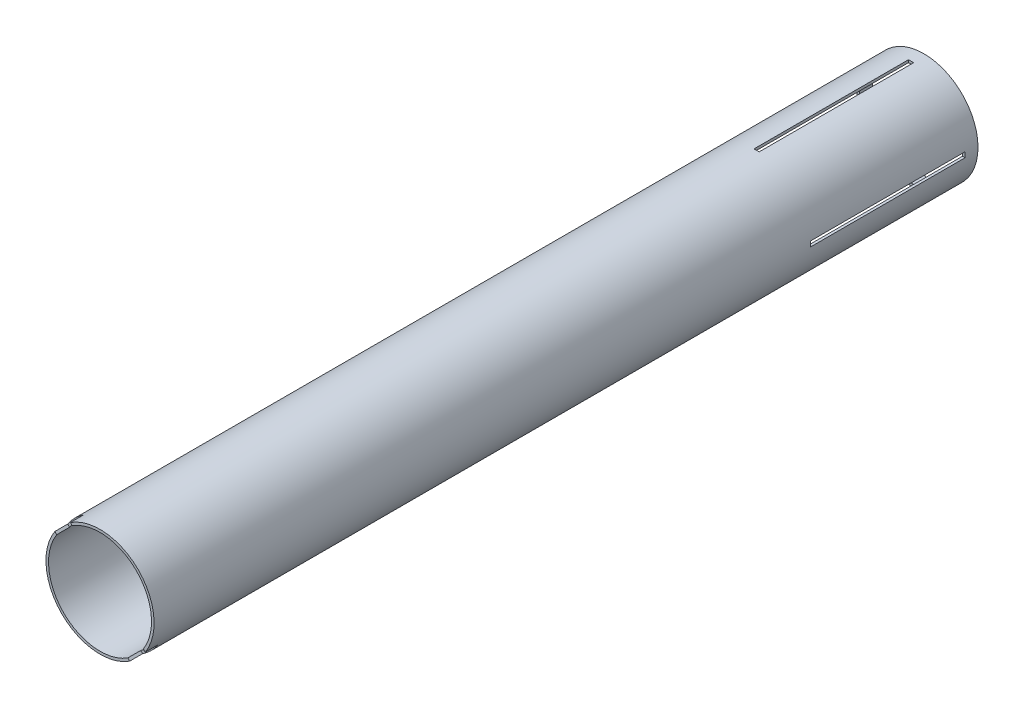
SolidWorks part; units mm, degrees
material "Corrugated Paper"
ref_plane "Front Plane" through (0, 0, 0) normal (0, 0, 1) x (1, 0, 0)
ref_plane "Top Plane" through (0, 0, 0) normal (0, 1, 0) x (1, 0, 0)
ref_plane "Right Plane" through (0, 0, 0) normal (1, 0, 0) x (0, 0, -1)
sketch "Sketch1" plane through (0, 0, 0) normal (0, 0, 1) x (1, 0, 0)
  circle A0 centre (0, 0) radius 50.8
  circle A1 centre (0, 0) radius 53.34
  dimension "D1" = 101.6
  dimension "D2" = 106.68
extrude "Boss-Extrude1" add sketch "Sketch1" along normal blind 812.8
sketch "Sketch2" plane through (0, 0, 0) normal (1, 0, 0) x (0, 0, -1)
  line L0 (0, -53.34) -> (0, 53.34) construction
  line L1 (-165.1, -2.54) -> (-12.7, -2.54)
  line L2 (-165.1, -2.54) -> (-165.1, 2.54)
  line L3 (-165.1, 2.54) -> (-12.7, 2.54)
  line L4 (-12.7, -2.54) -> (-12.7, 2.54)
  line L5 (-165.1, -2.54) -> (-12.7, 2.54) construction
  line L6 (-165.1, 2.54) -> (-12.7, -2.54) construction
  point P0 (-88.9, 0)
  dimension "D1" = 5.08
  dimension "D2" = 152.4
  dimension "D3" = 12.7
extrude "Cut-Extrude1" cut sketch "Sketch2" against normal up to next
ref_axis "Axis1" through (0, 0, -40.64) along (0, 0, 1)
pattern_circular "CirPattern1" count 4 every 90 about axis through (0, 0, -40.64) along (0, 0, 1) of "Cut-Extrude1"
ref_plane "Plane1" through (0, 0, 0) normal (-0.7071, 0.7071, 0) x (0, 0, 1)
sketch "Sketch3" plane through (0, 0, 0) normal (-0.7071, 0.7071, 0) x (0, 0, 1)
  line L0 (812.8, -53.34) -> (812.8, 53.34) construction
  line L1 (800.1, -10.795) -> (812.8, -10.795)
  line L2 (800.1, -10.795) -> (800.1, 10.795)
  line L3 (800.1, 10.795) -> (812.8, 10.795)
  line L4 (812.8, -10.795) -> (812.8, 10.795)
  line L5 (800.1, -10.795) -> (812.8, 10.795) construction
  line L6 (800.1, 10.795) -> (812.8, -10.795) construction
  point P0 (806.45, 0)
  point P7 (0, 0)
  dimension "D1" = 21.59
  dimension "D2" = 12.7
extrude "Cut-Extrude2" cut sketch "Sketch3" against normal through all both and the other way through all
